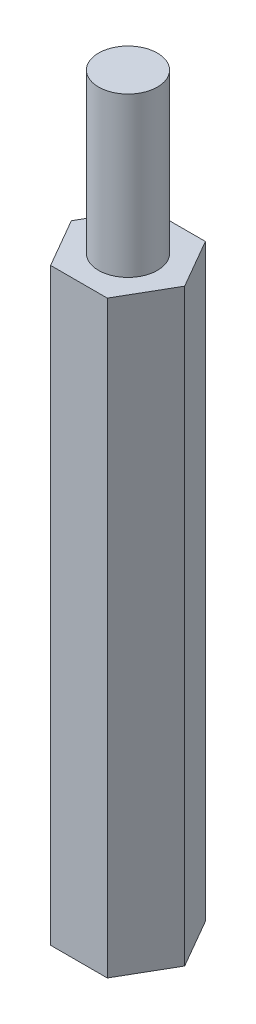
SolidWorks part; units mm, degrees
ref_plane "Front Plane" through (0, 0, 0) normal (0, 0, 1) x (1, 0, 0)
ref_plane "Top Plane" through (0, 0, 0) normal (0, 1, 0) x (1, 0, 0)
ref_plane "Right Plane" through (0, 0, 0) normal (1, 0, 0) x (0, 0, -1)
sketch "Sketch3" plane through (0, 0, 0) normal (0, 1, 0) x (1, 0, 0)
  line L1 (-2.8868, 0) -> (-1.4434, -2.5)
  line L2 (-1.4434, -2.5) -> (1.4434, -2.5)
  line L3 (1.4434, -2.5) -> (2.8868, 0)
  line L4 (2.8868, 0) -> (1.4434, 2.5)
  line L5 (1.4434, 2.5) -> (-1.4434, 2.5)
  line L6 (-1.4434, 2.5) -> (-2.8868, 0)
  circle A0 centre (0, 0) radius 2.5 construction
  dimension "D1" = 5
extrude "Boss-Extrude1" add sketch "Sketch3" along normal blind 30
sketch "Sketch5" plane through (0, 30, 0) normal (0, 1, 0) x (1, 0, 0)
  circle A0 centre (0, 0) radius 1.5
extrude "Boss-Extrude2" add sketch "Sketch5" along normal blind 8.0916
extrude "Boss-Extrude3" add sketch "Sketch5<2>" along normal blind 8
sketch "Sketch5<2>" plane through (0, 30, 0) normal (0, 1, 0) x (1, 0, 0) same geometry as "Sketch5"
